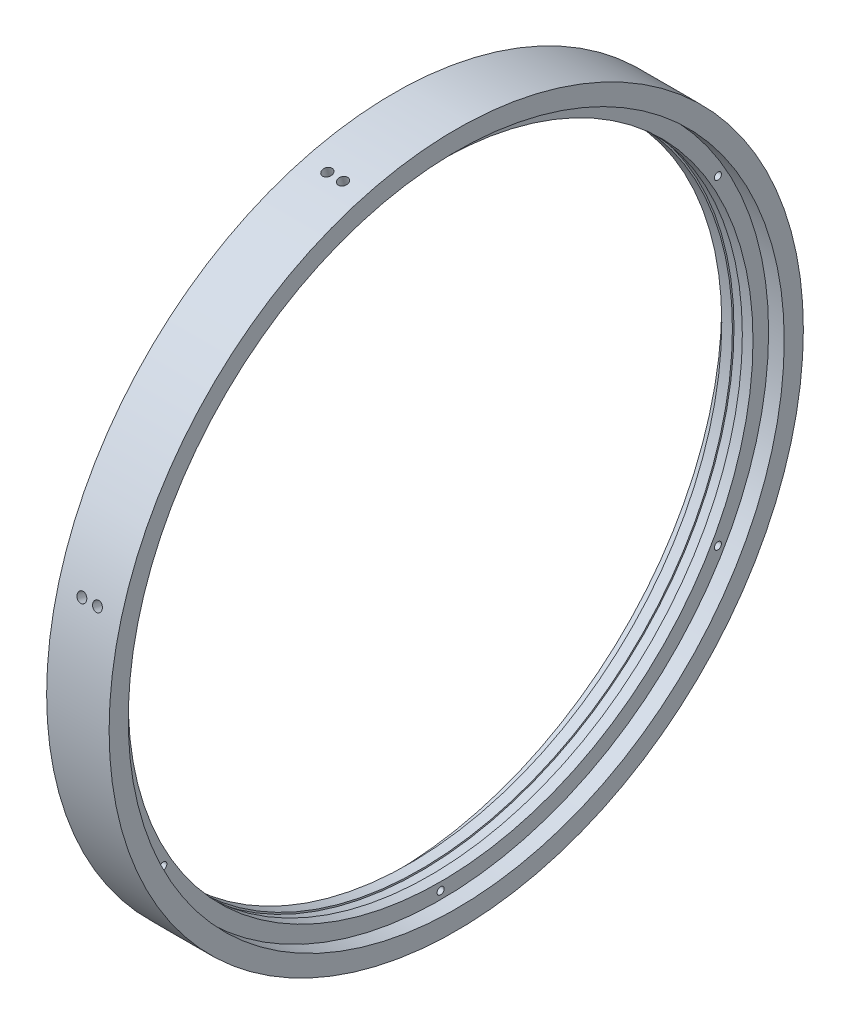
SolidWorks part; units mm, degrees
material "Delrin 2700 NC010, Low Viscosity Acetal Copolymer (SS)"
ref_plane "Front Plane" through (0, 0, 0) normal (0, 0, 1) x (1, 0, 0)
ref_plane "Top Plane" through (0, 0, 0) normal (0, 1, 0) x (1, 0, 0)
ref_plane "Right Plane" through (0, 0, 0) normal (1, 0, 0) x (0, 0, -1)
sketch "Sketch3" plane through (0, 0, 0) normal (0, 1, 0) x (1, 0, 0)
  line L0 (0, 0) -> (0, -111.125) construction
  line L1 (-10, -111.125) -> (10, -111.125)
  line L2 (10, -111.125) -> (10, -105)
  line L3 (10, -105) -> (5, -105)
  line L4 (5, -105) -> (5, -100)
  line L5 (5, -100) -> (1.5875, -100)
  line L6 (1.5875, -100) -> (1.5875, -100.5)
  line L7 (1.5875, -100.5) -> (-1.5875, -100.5)
  line L8 (-10, -111.125) -> (-10, -105)
  line L9 (-10, -105) -> (-5, -105)
  line L10 (-5, -105) -> (-5, -100)
  line L11 (-5, -100) -> (-1.5875, -100)
  line L12 (-1.5875, -100) -> (-1.5875, -100.5)
  line L13 (0, 0) -> (-91.3824, 0) construction
  point P16 (0, -100.5)
  dimension "D1" = 111.125
  dimension "D2" = 10
  dimension "D3" = 100
  dimension "D4" = 5
  dimension "D5" = 5
  dimension "D6" = 1.5875
  dimension "D7" = 0.5
revolve "Revolve1" add sketch "Sketch3" angle 360 about L13
chamfer "Chamfer1" [suppressed] distance 1.5 angle 45
sketch "Sketch4" plane through (5, 0, 0) normal (1, 0, 0) x (0, 0, -1)
  circle A0 centre (0, 0) radius 102.5 construction
  circle A1 centre (0, 0) radius 105
  circle A2 centre (0, 0) radius 105
  point P1 (0, -102.5)
  point P5 (-88.7676, -51.25)
  point P8 (-88.7676, 51.25)
  point P9 (0, 102.5)
  point P10 (88.7676, 51.25)
  point P11 (88.7676, -51.25)
  dimension "D2" = 205
  dimension "D1" = 0
  dimension "D3" = 6
hole_wizard "Tap Drill for #4-40 Tap1" positions "3DSketch1" profile "Sketch5" hole size "#4-40" standard "Ansi Inch"
sketch3d "3DSketch1"
  point P0 (5, -102.5, 0)
  point P3 (5, -51.25, 88.7676)
  point P6 (5, -51.25, -88.7676)
  point P9 (5, 51.25, -88.7676)
  point P12 (5, 102.5, 0)
  point P15 (5, 51.25, 88.7676)
sketch "Sketch5" plane through (5, -102.5, 0) normal (0, 1, 0) x (0, 0, -1)
  line L0 (0, 0) -> (0, 9.5692)
  line L1 (0, 9.5692) -> (1.1303, 8.89)
  line L2 (1.1303, 8.89) -> (1.1303, 0)
  line L5 (1.1303, 0) -> (0, 0)
  line L10 (0, 9.5692) -> (-1.1303, 8.89) construction
  line L11 (0, -6.35) -> (0, 107.95) construction
  dimension "Hole Dia." = 2.2606
  dimension "Hole Depth" = 8.89
  dimension "Drill Angle" = 118
sketch "Sketch6" plane through (-5, 0, 0) normal (-1, 0, 0) x (0, 0, 1)
  line L0 (0, 0) -> (0, -102.5) construction
  line L1 (0, 0) -> (51.25, -88.7676) construction
  line L2 (0, 0) -> (-51.25, -88.7676) construction
  line L3 (0, 0) -> (-102.5, 0) construction
  line L4 (0, 0) -> (-51.25, 88.7676) construction
  line L5 (0, 0) -> (51.25, 88.7676) construction
  line L6 (0, 0) -> (102.5, 0) construction
  circle A0 centre (0, 0) radius 102.5
  circle A1 centre (0, 0) radius 105
  circle A2 centre (0, 0) radius 105
  dimension "D2" = 205
  dimension "D3" = 30
  dimension "D1" = 0
  dimension "D4" = 6
hole_wizard "Tap Drill for #4-40 Tap2" positions "3DSketch2" profile "Sketch7" hole size "#4-40" standard "Ansi Inch"
sketch3d "3DSketch2"
  point P0 (-5, -88.7676, 51.25)
  point P3 (-5, 0, 102.5)
  point P6 (-5, 88.7676, 51.25)
  point P9 (-5, 88.7676, -51.25)
  point P12 (-5, 0, -102.5)
  point P15 (-5, -88.7676, -51.25)
sketch "Sketch7" plane through (-5, -88.7676, 51.25) normal (0, 1, 0) x (0, 0, 1)
  line L0 (0, 0) -> (0, 9.5692)
  line L1 (0, 9.5692) -> (1.1303, 8.89)
  line L2 (1.1303, 8.89) -> (1.1303, 0)
  line L5 (1.1303, 0) -> (0, 0)
  line L10 (0, 9.5692) -> (-1.1303, 8.89) construction
  line L11 (0, -6.35) -> (0, 107.95) construction
  dimension "Hole Dia." = 2.2606
  dimension "Hole Depth" = 8.89
  dimension "Drill Angle" = 118
ref_plane "Plane1" through (0, 107.3385, 28.7613) normal (0, 0.9659, 0.2588) x (-1, 0, 0)
sketch "Sketch8" plane through (0, 107.3385, 28.7613) normal (0, 0.9659, 0.2588) x (-1, 0, 0)
  line L0 (0, 0) -> (-10, 0) construction
  line L1 (-10, 111.125) -> (-10, -111.125) construction
  line L2 (0, 0) -> (10, 0) construction
  line L3 (10, -111.125) -> (10, 111.125) construction
  circle A0 centre (-2.5, 0) radius 1.524
  circle A1 centre (2.5, 0) radius 1.524
  dimension "D3" = 3.048
  dimension "D4" = 7.5
  dimension "D1" = 3.048
  dimension "D2" = 7.5
extrude "Cut-Extrude1" cut sketch "Sketch8" against normal blind 8.89
ref_axis "Axis1" through (-10, 0, 0) along (1, 0, 0)
pattern_circular "CirPattern1" count 6 over 360 about axis through (-10, 0, 0) along (1, 0, 0) of "Cut-Extrude1"
ref_axis "Axis2" through (-2.5, 98.0154, 26.2631) along (0, 0.9659, 0.2588)
ref_axis "Axis3" through (2.5, 98.0154, 26.2631) along (0, 0.9659, 0.2588)
